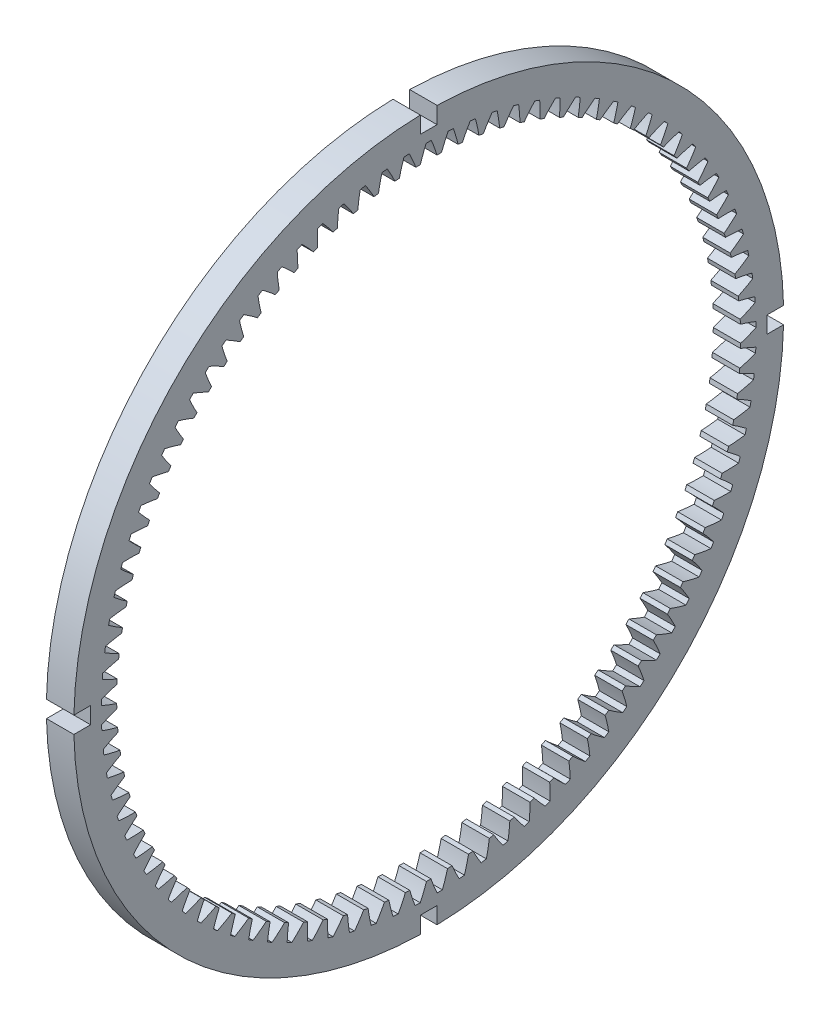
SolidWorks part; units mm, degrees
ref_plane "Plane1" through (0, 0, 0) normal (0, 0, 1) x (1, 0, 0)
ref_plane "Plane2" through (0, 0, 0) normal (0, 1, 0) x (1, 0, 0)
ref_plane "Plane3" through (0, 0, 0) normal (1, 0, 0) x (0, 0, -1)
sketch "HoldingSke" plane through (0, 0, 0) normal (0, 1, 0) x (1, 0, 0)
  line L0 (0, 0) -> (-0.0209, -0.3995)
  line L1 (-15, 0) -> (100, 0) construction
  line L2 (0, 0) -> (-2.1039, 2.3779)
  line L3 (0, 0) -> (-11.863, 4.5341)
  line L4 (0, 0) -> (-0.452, 8.6242)
  line L5 (0, 0) -> (-23.7986, -8.8762)
  line L6 (0, 0) -> (-10.5278, -7.1032)
  line L7 (-2.1039, 2.3779) -> (3.3635, 27.1825)
  line L8 (-76.2, 4.8779) -> (-54.61, 4.8779)
  line L9 (-71.009, 38.7566) -> (-53.1078, 45.2721)
  line L10 (-76.2, 71.12) -> (104.1128, 71.12)
  line L11 (0, 0) -> (-30, 0)
  line L12 (-76.2, 101.6) -> (-76.113, 101.6)
  line L13 (24.9733, 27.94) -> (52.9518, 28.4284)
  line L14 (24.9733, 27.94) -> (24.9743, 27.94)
  line L15 (24.9733, 27.94) -> (100.4006, 29.5858)
  circle A0 centre (0, 0) radius 50
  circle A1 centre (0, 0) radius 12.7
  circle A2 centre (0, 0) radius 12.7
  dimension "MHD" = 25.4
  dimension "Hub_dia" = 25.4
  dimension "Diameter" = 100
  dimension "Num_teeth" = 93
  dimension "Pitch" = 0.4
  dimension "Overall_len" = 25.4
  dimension "Show_teeth" = 93
  dimension "Thickness" = 12.7
  dimension "OAL" = 25.4001
  dimension "T_dim" = 21.59
  dimension "Ap" = 20
  dimension "H" = 19.05
  dimension "Pitch_radius" = 180.3128
  dimension "Width" = 30
  dimension "Backlash" = 0.087
  dimension "Addendum_fac" = 1
  dimension "Dedendum_fac" = 1.25
  dimension "Clearance_fac" = 0.25
  dimension "Dedendum_add" = 0.001
  dimension "Module" = 2.5
sketch "BasProSke" plane through (0, 0, 0) normal (0, 1, 0) x (1, 0, 0)
  line L0 (-10, 0) -> (60, 0) construction
  line L1 (0, 113.75) -> (0, 119.4014)
  line L2 (0, 113.75) -> (30, 113.75)
  line L3 (30, 113.75) -> (30, 119.4014)
  line L4 (30, 119.4014) -> (0, 119.4014)
  dimension "Thickness" = 30
  dimension "Diameter" = 238.8028
  dimension "Inside_diameter" = 227.5
revolve "Base-Revolve" add sketch "BasProSke" angle 360 about L0
sketch "TooCutSke" plane through (0, 0, 0) normal (1, 0, 0) x (0, 0, -1)
  line L3 (2.1809, 116.2295) -> (2.1809, 53.6633) construction
  line L4 (0, 0) -> (0, 59.563) construction
  line L5 (0, 0) -> (-2.3077, 68.2885) construction
  line L6 (-52.5279, 96.5964) -> (34.5007, 99.5374) construction
  circle A0 centre (0, 0) radius 116.25 construction
  circle A1 centre (0, 0) radius 119.376 construction
  circle A2 centre (0, 0) radius 98.3153 construction
  circle A3 centre (0, 0) radius 113.7246 construction
  arc A4 (3.0285, 113.6843) -> (0.949, 119.3722) centre (-52.5279, 96.5964) ccw
  arc A5 (3.0285, 113.6843) -> (-3.0285, 113.6843) centre (0, 0) ccw
  arc A6 (0.949, 119.3722) -> (-0.949, 119.3722) centre (0, 0) ccw
  arc A7 (-0.949, 119.3722) -> (-3.0285, 113.6843) centre (52.5279, 96.5964) ccw
  dimension "Pitch_dia" = 232.5
  dimension "Base_dia" = 196.6307
  dimension "Root_dia" = 238.752
  dimension "Overcut_dia" = 227.4492
  dimension "Flank_rad" = 58.125
  dimension "Half_ang" = 1.935
  dimension "Half_CT" = 2.1809
extrude "ToothCut" cut sketch "TooCutSke" along normal through all
fillet "Breaks" [suppressed] radius 0.25
fillet "RootFillets" [suppressed] radius 0.626
pattern_circular "TeethCuts" count 93 every 3.871 about axis through (-10, 0, 0) along (1, 0, 0) of "RootFillets", "Breaks", "ToothCut"
sketch "草圖2" plane through (0, 0, 0) normal (-1, 0, 0) x (0, 0, 1)
  line L0 (-148.9798, 0) -> (150.1653, 0) construction
  line L1 (0, 146.5311) -> (0, -139.1781) construction
  line L2 (3.05, 129.3655) -> (3.05, 123.2655)
  line L3 (-129.3655, 3.05) -> (-123.2655, 3.05)
  line L5 (-129.3655, -3.05) -> (-123.2655, -3.05)
  line L6 (-123.2655, 3.05) -> (-123.2655, -3.05)
  line L7 (3.05, 123.2655) -> (-3.05, 123.2655)
  line L8 (-3.05, 129.3655) -> (-3.05, 123.2655)
  line L9 (0, 148.9798) -> (0, -150.1653) construction
  line L10 (129.3655, -3.05) -> (123.2655, -3.05)
  line L11 (123.2655, -3.05) -> (123.2655, 3.05)
  line L12 (129.3655, 3.05) -> (123.2655, 3.05)
  line L13 (148.9798, 0) -> (-150.1653, 0) construction
  line L14 (-3.05, -129.3655) -> (-3.05, -123.2655)
  line L15 (-3.05, -123.2655) -> (3.05, -123.2655)
  line L16 (3.05, -129.3655) -> (3.05, -123.2655)
  line L17 (0, -148.9798) -> (0, 150.1653) construction
  circle A0 centre (0, 0) radius 119.4014 construction
  circle A1 centre (0, 0) radius 119.4014
  arc A2 (-129.3655, -3.05) -> (-3.05, -129.3655) centre (0, 0) ccw
  circle A3 centre (0, 0) radius 129.4014 construction
  arc A4 (-3.05, 129.3655) -> (-129.3655, 3.05) centre (0, 0) ccw
  arc A5 (129.3655, 3.05) -> (3.05, 129.3655) centre (0, 0) ccw
  arc A6 (3.05, -129.3655) -> (129.3655, -3.05) centre (0, 0) ccw
  point P14 (-123.2655, 0)
  point P36 (0, 0)
  dimension "D2" = 6.1
  dimension "D3" = 6.1
  dimension "D1" = 10
  dimension "D4" = 4
extrude "填料-伸長1" add sketch "草圖2" against normal up to surface (30 mm away) up to face at (30, 0, 119.4014)
sketch "草圖3" plane through (0, 0, 0) normal (-1, 0, 0) x (0, 0, 1)
  line L12 (-129.3655, 3.05) -> (-123.2655, 3.05)
  line L13 (-123.2655, 3.05) -> (-123.2655, -3.05)
  line L14 (-123.2655, -3.05) -> (-129.3655, -3.05)
  line L15 (-3.05, -129.3655) -> (-3.05, -123.2655)
  line L16 (-3.05, -123.2655) -> (3.05, -123.2655)
  line L17 (3.05, -123.2655) -> (3.05, -129.3655)
  line L18 (129.3655, -3.05) -> (123.2655, -3.05)
  line L19 (123.2655, -3.05) -> (123.2655, 3.05)
  line L20 (123.2655, 3.05) -> (129.3655, 3.05)
  line L21 (3.05, 129.3655) -> (3.05, 123.2655)
  line L22 (3.05, 123.2655) -> (-3.05, 123.2655)
  line L23 (-3.05, 123.2655) -> (-3.05, 129.3655)
  line L24 (-129.3655, 3.05) -> (-123.2655, 3.05)
  line L25 (-123.2655, 3.05) -> (-123.2655, -3.05)
  line L26 (-123.2655, -3.05) -> (-129.3655, -3.05)
  line L27 (-3.05, -129.3655) -> (-3.05, -123.2655)
  line L28 (-3.05, -123.2655) -> (3.05, -123.2655)
  line L29 (3.05, -123.2655) -> (3.05, -129.3655)
  line L30 (129.3655, -3.05) -> (123.2655, -3.05)
  line L31 (123.2655, -3.05) -> (123.2655, 3.05)
  line L32 (123.2655, 3.05) -> (129.3655, 3.05)
  line L33 (3.05, 129.3655) -> (3.05, 123.2655)
  line L34 (3.05, 123.2655) -> (-3.05, 123.2655)
  line L35 (-3.05, 123.2655) -> (-3.05, 129.3655)
  arc A4 (-3.05, 129.3655) -> (-129.3655, 3.05) centre (0, 0) ccw
  arc A5 (-129.3655, -3.05) -> (-3.05, -129.3655) centre (0, 0) ccw
  arc A6 (3.05, -129.3655) -> (129.3655, -3.05) centre (0, 0) ccw
  arc A7 (129.3655, 3.05) -> (3.05, 129.3655) centre (0, 0) ccw
  arc A8 (-3.05, 129.3655) -> (-129.3655, 3.05) centre (0, 0) ccw
  arc A9 (-129.3655, -3.05) -> (-3.05, -129.3655) centre (0, 0) ccw
  arc A10 (3.05, -129.3655) -> (129.3655, -3.05) centre (0, 0) ccw
  arc A11 (129.3655, 3.05) -> (3.05, 129.3655) centre (0, 0) ccw
  dimension "D1" = 0
extrude "除料-伸長1" cut sketch "草圖3" against normal blind 20
equation "' \"Module@HoldingSke\" = 6.35"
equation "' \"Num_teeth@HoldingSke\" = 24"
equation "' \"Ap@HoldingSke\" =  14.5"
equation "' \"Ap@HoldingSke\" = 14.5"
equation "' \"Width@HoldingSke\" = 12"
equation "' \"Diameter@HoldingSke\" = 8 * 25.4"
equation "' \"Show_teeth@HoldingSke\" = 100"
equation "' \"Backlash@HoldingSke\" = 0.009 * 25.4"
equation "' \"Addendum_fac@HoldingSke\" = 1.0"
equation "' \"Dedendum_fac@HoldingSke\" = 1.25"
equation "' \"Dedendum_add@HoldingSke\" = 0.00005 * 25.4"
equation "' \"Clearance_fac@HoldingSke\" = 0.25"
equation "\"Pitch@HoldingSke\" = 1 / \"Module@HoldingSke\" "
equation "\"Overcut_dia@TooCutSke\" = (\"Num_teeth@HoldingSke\" - 2 * \"Addendum_fac@HoldingSke\") / \"Pitch@HoldingSke\" - 0.002 * 25.4"
equation "\"Pitch_dia@TooCutSke\" = \"Num_teeth@HoldingSke\" / \"Pitch@HoldingSke\""
equation "\"Base_dia@TooCutSke\" = \"Num_teeth@HoldingSke\" / \"Pitch@HoldingSke\" * cos((\"Ap@HoldingSke\"  * 3.14159265 / 180)) * 0.90"
equation "\"Root_dia@TooCutSke\" = \"Num_teeth@HoldingSke\"  / \"Pitch@HoldingSke\" + 2 *  \"Dedendum_fac@HoldingSke\"/ \"Pitch@HoldingSke\" + \"Dedendum_add@HoldingSke\" * 2"
equation "\"Half_ang@TooCutSke\" = 180 / \"Num_teeth@HoldingSke\""
equation "\"Half_CT@TooCutSke\" = \"Num_teeth@HoldingSke\" / \"Pitch@HoldingSke\" * sin((3.14159265 / 2 / \"Num_teeth@HoldingSke\")) / 2 + 10 * \"Backlash@HoldingSke\" / 4"
equation "\"Flank_rad@TooCutSke\" = \"Num_teeth@HoldingSke\" / \"Pitch@HoldingSke\" / 4"
equation "\"Radius@RootFillets\"= \"Clearance_fac@HoldingSke\" / \"Pitch@HoldingSke\" + \"Dedendum_add@HoldingSke\""
equation "\"Break_rad@Breaks\" = 0.02 / \"Pitch@HoldingSke\" * 5"
equation "\"Num_teeth@TeethCuts\" = int( \"Show_teeth@HoldingSke\" ) + 1"
equation "\"Num_teeth@TeethCuts\" = ((sgn( \"Num_teeth@TeethCuts\" - \"Num_teeth@HoldingSke\" )-1)*( \"Num_teeth@TeethCuts\" - \"Num_teeth@HoldingSke\" ))/-2+ \"Num_teeth@HoldingSke\""
equation "\"Num_teeth@TeethCuts\" = ((sgn( \"Num_teeth@TeethCuts\" - 2.0)+1)*( \"Num_teeth@TeethCuts\" - 2.0))/2 +2.0"
equation "\"Angle@TeethCuts\" = 360.0 / \"Num_teeth@HoldingSke\""
equation "\"Diameter@BasProSke\" = \"Num_teeth@HoldingSke\"  / \"Pitch@HoldingSke\" + 2 *  \"Dedendum_fac@HoldingSke\"/ \"Pitch@HoldingSke\" + \"Dedendum_add@HoldingSke\" * 2 + 0.002 * 25.4"
equation "\"Diameter@BasProSke\" = ((sgn( \"Diameter@BasProSke\"  - \"Diameter@HoldingSke\" )+1)*( \"Diameter@BasProSke\"  - \"Diameter@HoldingSke\" ))/2 + \"Diameter@HoldingSke\""
equation "\"Inside_diameter@BasProSke\" =  (\"Num_teeth@HoldingSke\" - 2 * \"Addendum_fac@HoldingSke\") / \"Pitch@HoldingSke\" "
equation "\"Thickness@BasProSke\"  = \"Width@HoldingSke\""
